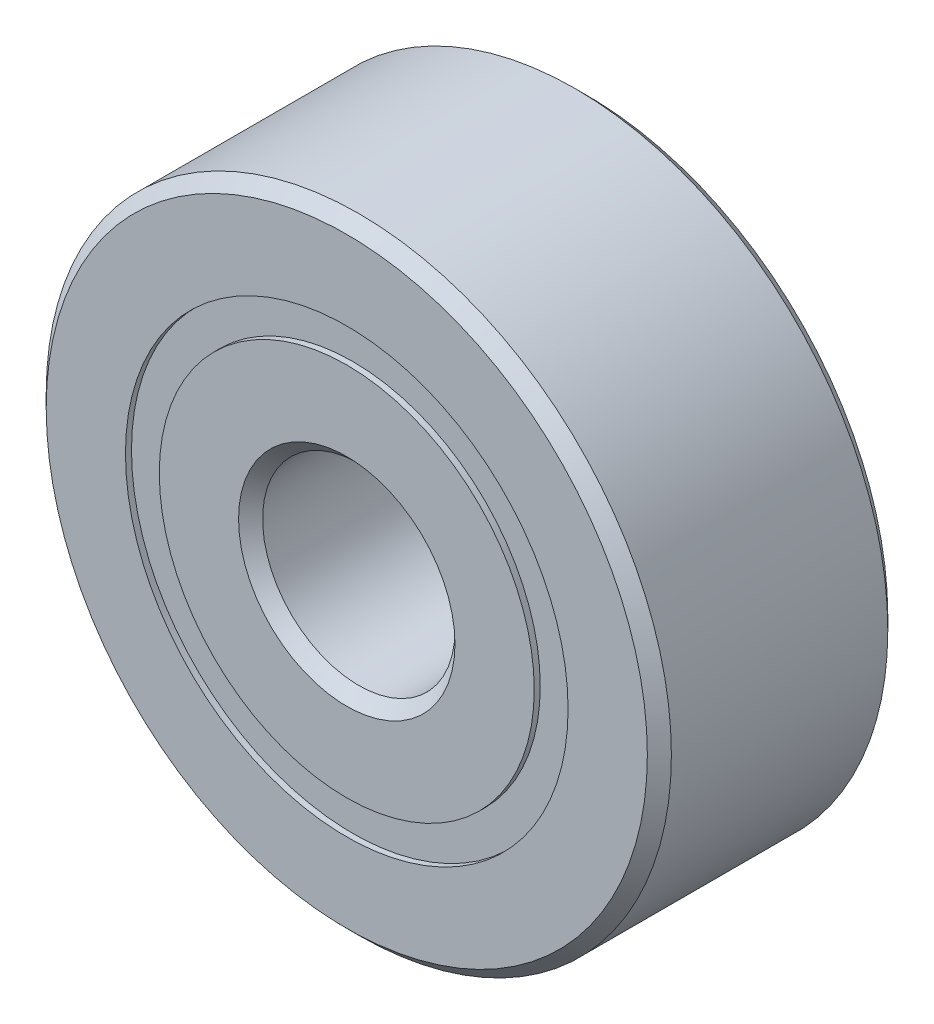
SolidWorks part; units mm, degrees
ref_plane "Front Plane" through (0, 0, 0) normal (0, 0, 1) x (1, 0, 0)
ref_plane "Top Plane" through (0, 0, 0) normal (0, 1, 0) x (1, 0, 0)
ref_plane "Right Plane" through (0, 0, 0) normal (1, 0, 0) x (0, 0, -1)
sketch "Sketch1" plane through (0, 0, 0) normal (1, 0, 0) x (0, 0, -1)
  line L0 (-2.5, 0) -> (2.5, 0) construction
  line L1 (0, 6.5) -> (0, -6.5) construction
  line L2 (2.25, 6.5) -> (-2.25, 6.5)
  line L3 (-2.25, 6.5) -> (-2.5, 6.25)
  line L4 (-2.5, 6.25) -> (-2.5, 4.6016)
  line L5 (-2.5, 4.6016) -> (-1.1111, 4.6016)
  line L6 (2.5, 4.6016) -> (1.1111, 4.6016)
  line L7 (2.5, 6.25) -> (2.5, 4.6016)
  line L8 (2.25, 6.5) -> (2.5, 6.25)
  line L9 (0, 6.5) -> (0, 4.25) construction
  line L10 (0, 4.25) -> (0, 2) construction
  arc A0 (-1.1111, 4.6016) -> (1.1111, 4.6016) centre (0, 4.25) cw
  point P14 (0, 2)
  dimension "D3" = 2.2222
  dimension "D1" = 45
  dimension "Width" = 5
  dimension "OD" = 13
  dimension "D2" = 0.25
  dimension "Shaft Dia" = 4
  dimension "D4" = 0.3516
revolve "Revolve1" add sketch "Sketch1" angle 360 about L0
sketch "Sketch3" plane through (0, 0, 0) normal (1, 0, 0) x (0, 0, -1)
  line L0 (-2.5, 3.8984) -> (-1.1111, 3.8984)
  line L1 (0, 6.5) -> (0, -6.5) construction
  line L2 (-2.5, 6.25) -> (-2.5, 4.6016) construction
  line L3 (-2.5, 3.8984) -> (-2.5, 2.25)
  line L4 (-2.25, 6.5) -> (-2.5, 6.25) construction
  line L5 (-2.5, 2.25) -> (-2.25, 2)
  line L6 (-2.25, 2) -> (2.25, 2)
  line L7 (2.25, 6.5) -> (2.25, -6.5) construction
  line L8 (2.25, 2) -> (2.5, 2.25)
  line L9 (2.5, -6.25) -> (2.5, 6.25) construction
  line L10 (2.5, 2.25) -> (2.5, 3.8984)
  line L11 (2.5, 3.8984) -> (1.1111, 3.8984)
  line L13 (2.25, 6.5) -> (2.5, 6.25) construction
  arc A0 (1.1111, 4.6016) -> (-1.1111, 4.6016) centre (0, 4.25) ccw construction
  arc A1 (1.1111, 3.8984) -> (-1.1111, 3.8984) centre (0, 4.25) cw
revolve "Revolve3" add sketch "Sketch3" angle 360 about L0
sketch "Sketch4" plane through (0, 0, 0) normal (1, 0, 0) x (0, 0, -1)
  line L0 (-1.1654, 4.25) -> (1.1654, 4.25)
  arc A2 (-1.1654, 4.25) -> (1.1654, 4.25) centre (0, 4.25) cw
  arc A3 (1.1111, 4.6016) -> (-1.1111, 4.6016) centre (0, 4.25) ccw construction
revolve "Revolve4" add sketch "Sketch4" angle 360 about L0
ref_axis "Axis1" through (0, 0, -2.5) along (0, 0, 1)
pattern_circular "CirPattern1" count 12 every 30 about axis through (0, 0, -2.5) along (0, 0, 1) of bodies 104
sketch "Sketch5" plane through (0, 0, 0) normal (1, 0, 0) x (0, 0, -1)
  line L0 (-2.5, 4.6016) -> (-1.1111, 4.6016) construction
  line L1 (-2.375, 4.6016) -> (-1.1654, 4.6016)
  line L2 (-2.375, 4.6016) -> (-2.375, 3.8984)
  line L3 (-2.375, 3.8984) -> (-1.1654, 3.8984)
  line L4 (-1.1654, 4.6016) -> (-1.1654, 3.8984)
  line L5 (-2.5, 3.8984) -> (-1.1111, 3.8984) construction
  line L6 (2.5, 4.6016) -> (1.1111, 4.6016) construction
  line L7 (2.375, 4.6016) -> (1.1654, 4.6016)
  line L8 (2.375, 4.6016) -> (2.375, 3.8984)
  line L9 (2.375, 3.8984) -> (1.1654, 3.8984)
  line L10 (1.1654, 4.6016) -> (1.1654, 3.8984)
  line L11 (2.5, 3.8984) -> (1.1111, 3.8984) construction
  line L12 (-2.25, 6.5) -> (-2.5, 6.25) construction
  point P18 (-2.375, 6.375)
revolve "Revolve5" add sketch "Sketch5" angle 360 about L0
sketch "Sketch6" plane through (0, 0, 0) normal (1, 0, 0) x (0, 0, -1)
  line L0 (2.5, 0) -> (-2.5, 0) construction
  line L1 (2.5, 4.6016) -> (1.7126, 4.6016)
  line L2 (2.5, 4.6016) -> (2.5, 6.9469)
  line L3 (2.5, 6.9469) -> (1.7126, 6.9469)
  line L4 (1.7126, 4.6016) -> (1.7126, 6.9469)
  dimension "Th" = 0.7874
  dimension "Flange OD" = 13.8938
revolve "Revolve6" [suppressed] add sketch "Sketch6" angle 360 about L0
equation "\"D2@Sketch1\" = \"Width@Sketch1\"*.05"
equation "\"D3@Sketch1\" = \"Width@Sketch1\"/2.25"
equation "\"D4@Sketch1\" = (((\"OD@Sketch1\"-\"Width@Sketch1\")/2)/3.25)/3.5"
equation "\"D2@CirPattern1\" = 360/\"Balls@CirPattern1\""
